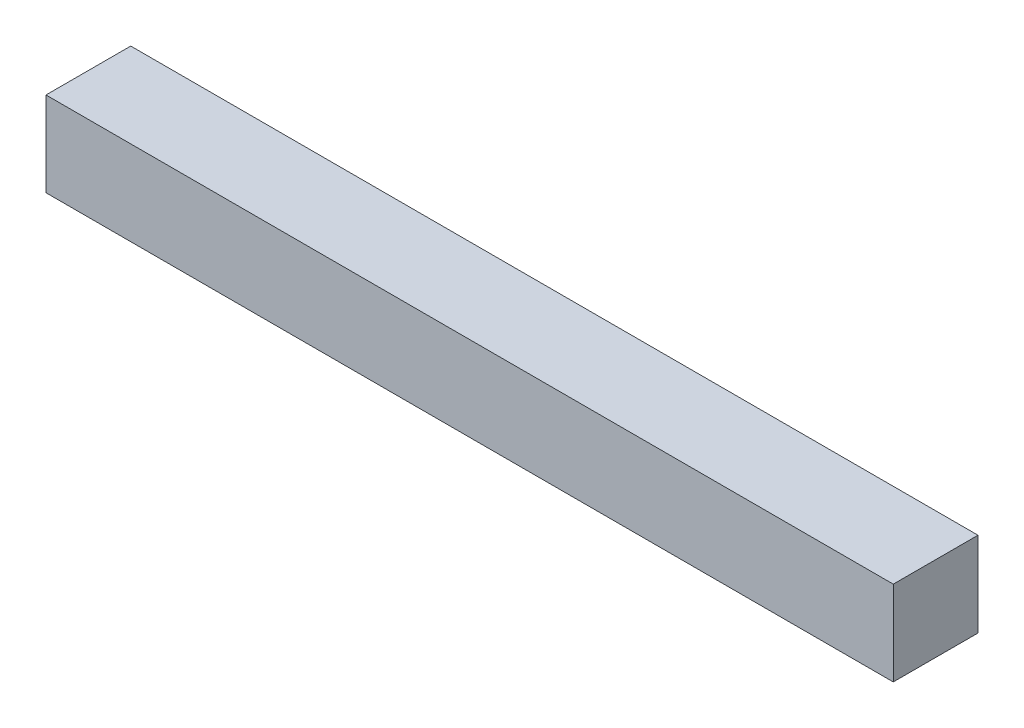
SolidWorks part; units mm, degrees
ref_plane "Plan de face" through (0, 0, 0) normal (0, 0, 1) x (1, 0, 0)
ref_plane "Plan de dessus" through (0, 0, 0) normal (0, 1, 0) x (1, 0, 0)
ref_plane "Plan de droite" through (0, 0, 0) normal (1, 0, 0) x (0, 0, -1)
sketch "Esquisse1" plane through (0, 0, 0) normal (1, 0, 0) x (0, 0, -1)
  line L1 (-5, -5) -> (5, -5)
  line L2 (-5, -5) -> (-5, 5)
  line L3 (-5, 5) -> (5, 5)
  line L4 (5, -5) -> (5, 5)
  line L5 (-5, -5) -> (5, 5) construction
  line L6 (-5, 5) -> (5, -5) construction
  point P0 (0, 0)
  dimension "D1" = 10
  dimension "D2" = 10
extrude "Boss.-Extru.1" add sketch "Esquisse1" along normal blind 100
ref_plane "Plan1" through (25, 0, 0) normal (-1, 0, 0) x (0, 0, 1)
sketch "Esquisse2" plane through (0, 5, 0) normal (0, 1, 0) x (1, 0, 0)
  line L0 (20, 5) -> (20, -5) construction
  line L1 (100, 5) -> (0, 5) construction
  line L2 (100, -5) -> (0, -5) construction
  line L3 (0, 5) -> (0, -5) construction
  dimension "D1" = 20
sketch "Esquisse4" plane through (25, 0, 0) normal (-1, 0, 0) x (0, 0, 1)
  line L0 (-5, 5) -> (5, 5)
  line L1 (-5, 5) -> (5, 5)
  line L2 (5, 5) -> (5, -5)
  line L3 (5, 5) -> (5, -5)
  line L4 (5, -5) -> (-5, -5)
  line L5 (5, -5) -> (-5, -5)
  line L6 (-5, -5) -> (-5, 5)
  line L7 (-5, -5) -> (-5, 5)
ref_axis "Axe1" through (-5, 0, 0) along (1, 0, 0)
equation "\"D2@Esquisse1\"=\"D1@Esquisse1\""
